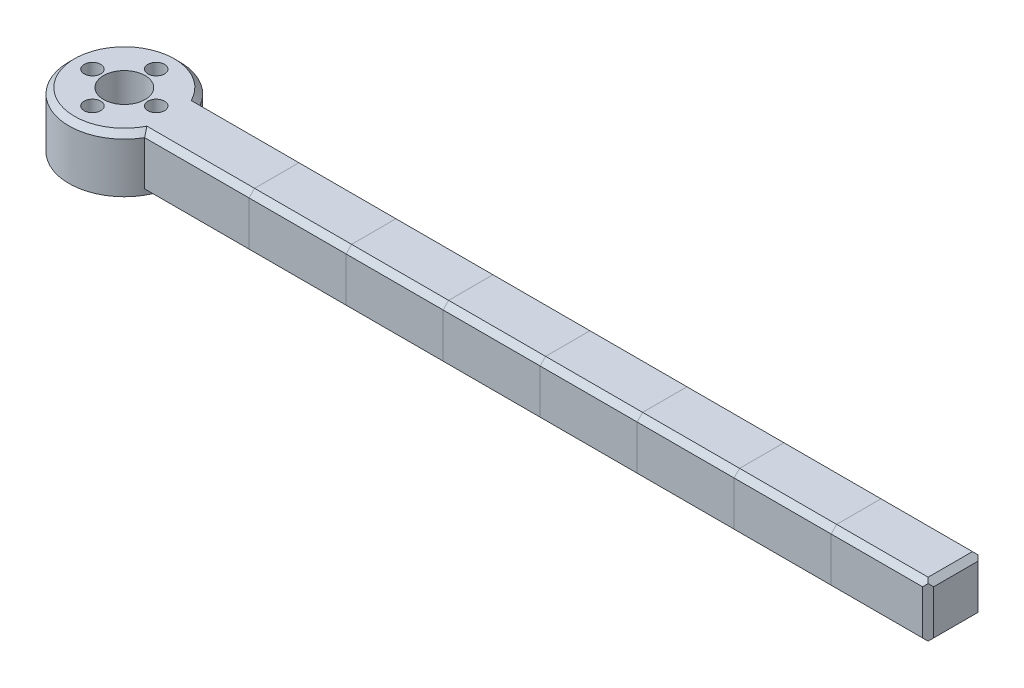
SolidWorks part; units mm, degrees
ref_plane "Front Plane" through (0, 0, 0) normal (0, 0, 1) x (1, 0, 0)
ref_plane "Top Plane" through (0, 0, 0) normal (0, 1, 0) x (1, 0, 0)
ref_plane "Right Plane" through (0, 0, 0) normal (1, 0, 0) x (0, 0, -1)
sketch "Sketch1" plane through (0, 0, 0) normal (0, 1, 0) x (1, 0, 0)
  circle A0 centre (0, 0) radius 20
  circle A1 centre (0, 0) radius 7.5
  circle A2 centre (0, 0) radius 11.5 construction
  circle A3 centre (0, 11.5) radius 1.6
  circle A4 centre (11.5, 0) radius 1.6
  circle A5 centre (0, -11.5) radius 1.6
  circle A6 centre (-11.5, 0) radius 1.6
  dimension "D1" = 40
  dimension "D2" = 15
  dimension "D3" = 23
  dimension "D4" = 3.2
extrude "Boss-Extrude1" add sketch "Sketch1" along normal blind 20
sketch "Sketch2" plane through (0, 20, 0) normal (0, 1, 0) x (1, 0, 0)
  circle A0 centre (0, 11.5) radius 3
  circle A1 centre (11.5, 0) radius 3
  circle A2 centre (0, -11.5) radius 3
  circle A3 centre (-11.5, 0) radius 3
  dimension "D1" = 6
extrude "Cut-Extrude2" cut sketch "Sketch2" against normal offset from surface (18 mm away) 2 up to face at (0, 0, 20)
sketch "Sketch3" plane through (0, 20, 0) normal (0, 1, 0) x (1, 0, 0)
  line L0 (20, 0) -> (55, 0) construction
  line L1 (55, -10) -> (55, 10)
  line L2 (55, 10) -> (17.3205, 10)
  line L3 (55, -10) -> (17.3205, -10)
  circle A0 centre (0, 0) radius 20 construction
  arc A1 (17.3205, -10) -> (17.3205, 10) centre (0, 0) ccw
  point P9 (55, 0)
  dimension "D1" = 35
  dimension "D2" = 20
extrude "Boss-Extrude2" add sketch "Sketch3" against normal up to surface (20 mm away) up to face at (0, 0, 20)
sketch "Sketch4" plane through (55, 0, 0) normal (1, 0, 0) x (0, 0, -1)
  line L4 (-10, 0) -> (10, 0)
  line L5 (10, 0) -> (10, 20)
  line L6 (10, 20) -> (-10, 20)
  line L7 (-10, 20) -> (-10, 0)
  line L8 (-10, 0) -> (10, 0)
  line L9 (10, 0) -> (10, 20)
  line L10 (10, 20) -> (-10, 20)
  line L11 (-10, 20) -> (-10, 0)
  dimension "D1" = 0
extrude "Boss-Extrude3" add sketch "Sketch4" along normal blind 35 separate body
pattern_linear "LPattern1" count 7 spacing 35 along (1, 0, 0) of "Boss-Extrude3"
chamfer "Chamfer2" distance 2 angle 45 4 edges at (72.5, 0, 10) (72.5, 0, -10) (72.5, 20, 10) (72.5, 20, -10)
chamfer "Chamfer3" distance 2 angle 45 4 edges at (107.5, 0, 10) (107.5, 20, 10) (107.5, 0, -10) (107.5, 20, -10)
chamfer "Chamfer4" distance 2 angle 45 4 edges at (142.5, 0, 10) (142.5, 20, 10) (142.5, 0, -10) (142.5, 20, -10)
chamfer "Chamfer5" distance 2 angle 45 4 edges at (177.5, 0, 10) (177.5, 20, 10) (177.5, 0, -10) (177.5, 20, -10)
chamfer "Chamfer6" distance 2 angle 45 4 edges at (212.5, 0, 10) (212.5, 20, 10) (212.5, 0, -10) (212.5, 20, -10)
chamfer "Chamfer7" distance 2 angle 45 4 edges at (247.5, 0, 10) (247.5, 20, 10) (247.5, 0, -10) (247.5, 20, -10)
chamfer "Chamfer8" distance 2 angle 45 4 edges at (282.5, 0, 10) (282.5, 20, 10) (282.5, 0, -10) (282.5, 20, -10)
chamfer "Chamfer9" distance 2 angle 45 5 edges at (36.1603, 0, 10) (36.1603, 0, -10) (36.1603, 20, 10) (-20, 20, 0) (36.1603, 20, -10)
chamfer "Chamfer10" distance 2 angle 45 4 edges at (300, 10, 10) (300, 10, -10) (300, 20, 0) (300, 0, 0)
sketch "Sketch5" plane through (0, 2, 0) normal (0, 1, 0) x (1, 0, 0)
  line L6 (-1.6, 8.9623) -> (-1.6, 14.0377)
  line L8 (9.9, -2.5377) -> (9.9, 2.5377)
  line L10 (13.1, -2.5377) -> (13.1, 2.5377)
  line L11 (9.9, -2.5377) -> (13.1, 2.5377) construction
  line L12 (9.9, 2.5377) -> (13.1, -2.5377) construction
  line L14 (-1.6, -14.0377) -> (-1.6, -8.9623)
  line L16 (1.6, -14.0377) -> (1.6, -8.9623)
  line L17 (-1.6, -14.0377) -> (1.6, -8.9623) construction
  line L18 (-1.6, -8.9623) -> (1.6, -14.0377) construction
  line L20 (-13.1, -2.5377) -> (-13.1, 2.5377)
  line L22 (-9.9, -2.5377) -> (-9.9, 2.5377)
  line L23 (-13.1, -2.5377) -> (-9.9, 2.5377) construction
  line L24 (-13.1, 2.5377) -> (-9.9, -2.5377) construction
  line L26 (1.6, 8.9623) -> (1.6, 14.0377)
  line L27 (-1.6, 8.9623) -> (1.6, 14.0377) construction
  line L28 (-1.6, 14.0377) -> (1.6, 8.9623) construction
  arc A0 (1.6, 14.0377) -> (-1.6, 14.0377) centre (0, 11.5) ccw
  circle A1 centre (11.5, 0) radius 3 construction
  circle A2 centre (0, -11.5) radius 3 construction
  circle A3 centre (-11.5, 0) radius 3 construction
  circle A4 centre (-11.5, 0) radius 1.6 construction
  arc A5 (-13.1, -2.5377) -> (-9.9, -2.5377) centre (-11.5, 0) ccw
  circle A6 centre (11.5, 0) radius 1.6 construction
  circle A7 centre (0, -11.5) radius 1.6 construction
  circle A8 centre (0, 11.5) radius 3 construction
  circle A9 centre (0, 11.5) radius 1.6 construction
  arc A10 (-1.6, 8.9623) -> (1.6, 8.9623) centre (0, 11.5) ccw
  arc A11 (9.9, -2.5377) -> (13.1, -2.5377) centre (11.5, 0) ccw
  arc A12 (1.6, -8.9623) -> (-1.6, -8.9623) centre (0, -11.5) ccw
  arc A13 (-9.9, 2.5377) -> (-13.1, 2.5377) centre (-11.5, 0) ccw
  arc A14 (13.1, 2.5377) -> (9.9, 2.5377) centre (11.5, 0) ccw
  arc A15 (-1.6, -14.0377) -> (1.6, -14.0377) centre (0, -11.5) ccw
  point P0 (0, 11.5)
  point P1 (0, 11.5)
  point P8 (11.5, 0)
  point P16 (0, -11.5)
  point P24 (-11.5, 0)
extrude "Cut-Extrude3" cut sketch "Sketch5" against normal blind 0.2
sketch "Sketch6" plane through (0, 1.8, 0) normal (0, 1, 0) x (1, 0, 0)
  line L0 (1.6, 11.5) -> (1.6, 14.0377) construction
  line L1 (-1.6, 9.9) -> (1.6, 9.9)
  line L2 (-1.6, 9.9) -> (-1.6, 13.1)
  line L3 (-1.6, 13.1) -> (1.6, 13.1)
  line L4 (1.6, 9.9) -> (1.6, 13.1)
  line L5 (-1.6, 9.9) -> (1.6, 13.1) construction
  line L6 (-1.6, 13.1) -> (1.6, 9.9) construction
  line L7 (13.1, -2.5377) -> (13.1, 2.5377) construction
  line L8 (9.9, -1.6) -> (13.1, -1.6)
  line L9 (9.9, -1.6) -> (9.9, 1.6)
  line L10 (9.9, 1.6) -> (13.1, 1.6)
  line L11 (13.1, -1.6) -> (13.1, 1.6)
  line L12 (9.9, -1.6) -> (13.1, 1.6) construction
  line L13 (9.9, 1.6) -> (13.1, -1.6) construction
  line L14 (1.6, -14.0377) -> (1.6, -8.9623) construction
  line L15 (-1.6, -13.1) -> (1.6, -13.1)
  line L16 (-1.6, -13.1) -> (-1.6, -9.9)
  line L17 (-1.6, -9.9) -> (1.6, -9.9)
  line L18 (1.6, -13.1) -> (1.6, -9.9)
  line L19 (-1.6, -13.1) -> (1.6, -9.9) construction
  line L20 (-1.6, -9.9) -> (1.6, -13.1) construction
  line L21 (-9.9, -2.5377) -> (-9.9, 2.5377) construction
  line L22 (-13.1, -1.6) -> (-9.9, -1.6)
  line L23 (-13.1, -1.6) -> (-13.1, 1.6)
  line L24 (-13.1, 1.6) -> (-9.9, 1.6)
  line L25 (-9.9, -1.6) -> (-9.9, 1.6)
  line L26 (-13.1, -1.6) -> (-9.9, 1.6) construction
  line L27 (-13.1, 1.6) -> (-9.9, -1.6) construction
  arc A0 (-9.9, 0) -> (-13.1, 0) centre (-11.5, 0) ccw construction
  arc A1 (1.6, 11.5) -> (-1.6, 11.5) centre (0, 11.5) ccw construction
  arc A2 (13.1, 0) -> (9.9, 0) centre (11.5, 0) ccw construction
  arc A3 (1.6, -11.5) -> (-1.6, -11.5) centre (0, -11.5) ccw construction
  point P0 (0, 11.5)
  point P8 (11.5, 0)
  point P16 (0, -11.5)
  point P24 (-11.5, 0)
extrude "Cut-Extrude4" cut sketch "Sketch6" against normal blind 0.2
